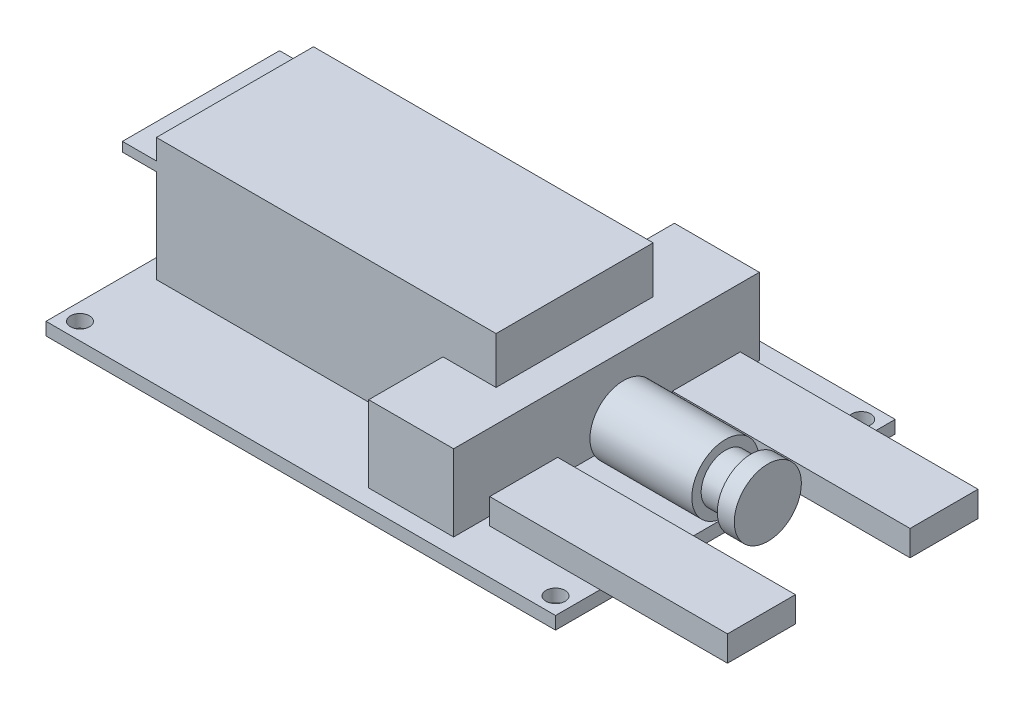
SolidWorks part; units mm, degrees
ref_plane "Front Plane" through (0, 0, 0) normal (0, 0, 1) x (1, 0, 0)
ref_plane "Top Plane" through (0, 0, 0) normal (0, 1, 0) x (1, 0, 0)
ref_plane "Right Plane" through (0, 0, 0) normal (1, 0, 0) x (0, 0, -1)
sketch "Sketch1" plane through (0, 0, 0) normal (0, 1, 0) x (1, 0, 0)
  line L0 (0, 0) -> (0, 0.6121) construction
  line L1 (-30, -20) -> (30, -20)
  line L2 (-30, -20) -> (-30, 20)
  line L3 (-30, 20) -> (30, 20)
  line L4 (30, -20) -> (30, 20)
  line L5 (-30, -20) -> (30, 20) construction
  line L6 (-30, 20) -> (30, -20) construction
  line L7 (0, 20) -> (0, 0) construction
  line L8 (0, 0) -> (30, 0) construction
  circle A0 centre (-28, 18) radius 1.125
  circle A1 centre (28, 18) radius 1.125
  circle A2 centre (-28, -18) radius 1.125
  circle A3 centre (28, -18) radius 1.125
  point P0 (0, 0)
  dimension "D3" = 2
  dimension "D1" = 40
  dimension "D2" = 60
  dimension "D4" = 2
extrude "Boss-Extrude1" add sketch "Sketch1" against normal blind 1.5
ref_plane "Plane1" through (30, 0, 0) normal (1, 0, 0) x (0, 0, -1)
sketch "Sketch2" plane through (30, 0, 0) normal (1, 0, 0) x (0, 0, -1)
  line L0 (-20, -1.5) -> (20, -1.5) construction
  line L2 (0, 0) -> (0, 4.9425) construction
  circle A0 centre (0, 4) radius 3.95
  dimension "D1" = 7.9
  dimension "D2" = 0
  dimension "D3" = 5.5
extrude "Boss-Extrude2" add sketch "Sketch2" against normal blind 12
sketch "Sketch4" plane through (30, 0, 0) normal (1, 0, 0) x (0, 0, -1)
  circle A1 centre (0, 4) radius 2.85
  dimension "D2" = 5.7
extrude "Boss-Extrude3" add sketch "Sketch4" along normal blind 3
extrude "Boss-Extrude4" add sketch "Sketch2<2>" along normal blind 2 from offset 3
sketch "Sketch2<2>" plane through (30, 0, 0) normal (1, 0, 0) x (0, 0, -1) same geometry as "Sketch2"
ref_plane "Plane2" through (30, 0, 0) normal (1, 0, 0) x (0, 0, -1)
sketch "Sketch5" plane through (30, 0, 0) normal (1, 0, 0) x (0, 0, -1)
  line L0 (-20, -1.5) -> (-20, 0) construction
  line L1 (-14.75, 3) -> (-6.75, 3)
  line L2 (-14.75, 3) -> (-14.75, 0)
  line L3 (-14.75, 0) -> (-6.75, 0)
  line L4 (-6.75, 3) -> (-6.75, 0)
  line L5 (0, 0) -> (0, 4.3139) construction
  line L6 (14.75, 0) -> (6.75, 0)
  line L7 (6.75, 3) -> (6.75, 0)
  line L8 (14.75, 3) -> (14.75, 0)
  line L9 (14.75, 3) -> (6.75, 3)
  dimension "D1" = 0
  dimension "D2" = 5.25
  dimension "D3" = 8
  dimension "D4" = 3
extrude "Boss-Extrude5" add sketch "Sketch5" along normal blind 15 and the other way blind 13 separate body
sketch "Sketch6" plane through (0, 0, 0) normal (0, 1, 0) x (1, 0, 0)
  line L0 (30, 20) -> (-30, 20) construction
  line L1 (6, 18) -> (16, 18)
  line L2 (6, 18) -> (6, -18)
  line L3 (6, -18) -> (16, -18)
  line L4 (16, 18) -> (16, -18)
  line L5 (17, -6.75) -> (17, -14.75) construction
  line L6 (-30, -20) -> (30, -20) construction
  dimension "D1" = 2
  dimension "D2" = 10
  dimension "D3" = 1
  dimension "D4" = 2
extrude "Boss-Extrude6" add sketch "Sketch6" along normal blind 9
sketch "Sketch11" plane through (0, 0, 0) normal (0, 1, 0) x (1, 0, 0)
  line L0 (-31.75, 0) -> (-13.0421, 0) construction
  line L1 (-31.75, 9.25) -> (12.25, 9.25)
  line L2 (-31.75, 9.25) -> (-31.75, -9.25)
  line L3 (-31.75, -9.25) -> (12.25, -9.25)
  line L4 (12.25, 9.25) -> (12.25, -9.25)
  line L5 (0, 0) -> (-11.3214, 0) construction
  line L6 (-30, 20) -> (-30, -20) construction
  dimension "D1" = 44
  dimension "D2" = 18.5
  dimension "D3" = 1.75
extrude "Boss-Extrude11" add sketch "Sketch11" along normal blind 14.5
sketch "Sketch12" plane through (-31.75, 0, 0) normal (-1, 0, 0) x (0, 0, 1)
  line L0 (-9.25, 14.5) -> (-9.25, 0) construction
  line L1 (-9.25, 11) -> (9.25, 11)
  line L2 (-9.25, 11) -> (-9.25, 0)
  line L3 (-9.25, 0) -> (9.25, 0)
  line L4 (9.25, 11) -> (9.25, 0)
  line L5 (9.25, 0) -> (-9.25, 0) construction
  line L6 (9.25, 0) -> (9.25, 9) construction
  line L7 (-9.25, 14.5) -> (9.25, 14.5) construction
  dimension "D1" = 3.5
extrude "Cut-Extrude1" cut sketch "Sketch12" against normal blind 4
sketch "Sketch13" plane through (-31.75, 0, 0) normal (-1, 0, 0) x (0, 0, 1)
  line L0 (9.25, 14.5) -> (9.25, 11) construction
  line L1 (-9.25, 14.5) -> (9.25, 14.5)
  line L2 (-9.25, 14.5) -> (-9.25, 12.1)
  line L3 (-9.25, 12.1) -> (9.25, 12.1)
  line L4 (9.25, 14.5) -> (9.25, 12.1)
  line L5 (9.25, 11) -> (-9.25, 11) construction
  dimension "D1" = 1.1
extrude "Cut-Extrude2" cut sketch "Sketch13" against normal blind 4
sketch "Sketch15" plane through (35, 0, 0) normal (1, 0, 0) x (0, 0, -1)
  circle A0 centre (0, 4) radius 5.5
extrude "Boss-Extrude12" [suppressed] add sketch "Sketch15" along normal blind 55 draft 1
